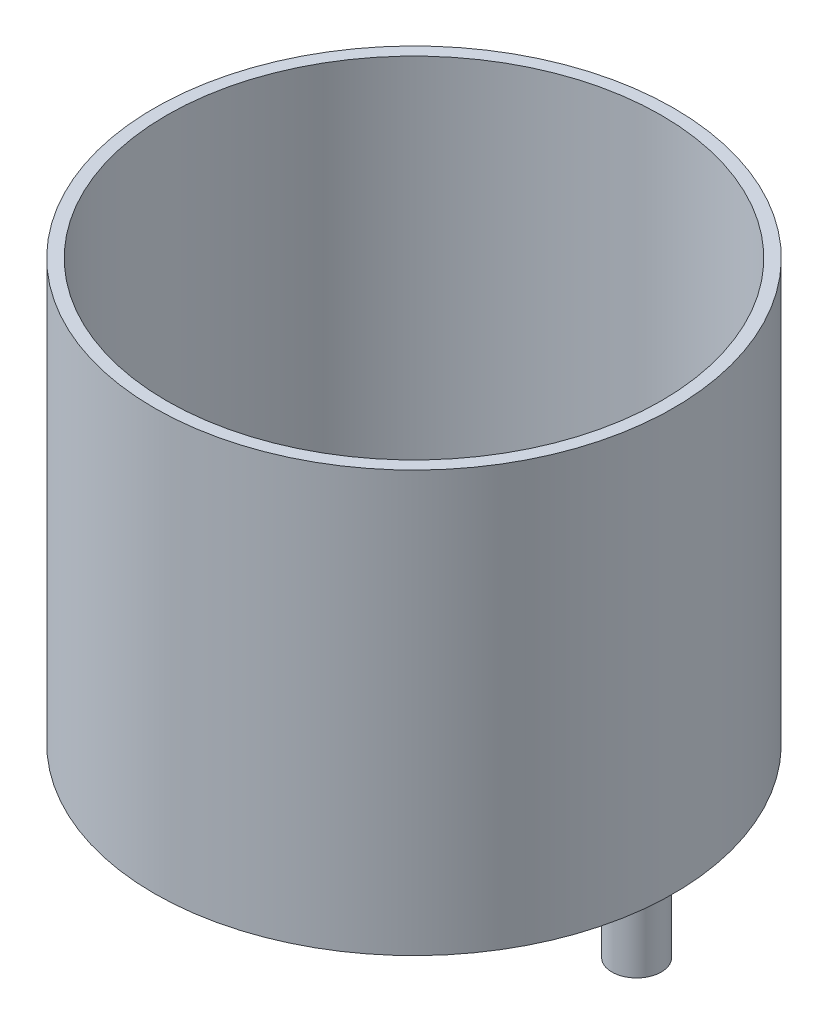
SolidWorks part; units mm, degrees
ref_plane "Front Plane" through (0, 0, 0) normal (0, 0, 1) x (1, 0, 0)
ref_plane "Top Plane" through (0, 0, 0) normal (0, 1, 0) x (1, 0, 0)
ref_plane "Right Plane" through (0, 0, 0) normal (1, 0, 0) x (0, 0, -1)
sketch "Compartment" plane through (0, 0, 0) normal (0, 0, 1) x (1, 0, 0)
  line L3 (105, -80) -> (0, -80)
  line L6 (100, 90) -> (105, 90)
  line L9 (100, 90) -> (100, -75)
  line L10 (100, -75) -> (0, -75)
  line L11 (0, -75) -> (0, -80)
  line L14 (105, 90) -> (105, -80)
  dimension "D1" = 165
  dimension "D2" = 5
  dimension "D5" = 100
  dimension "D6" = 5
  dimension "D9" = 80
ref_axis "Axis1" through (0, 0, 0) along (0, 1, 0)
revolve "Revolve1" add sketch "Compartment" angle 360 about axis through (0, 0, 0) along (0, 1, 0)
sketch "Motor Hole" plane through (0, -80, 0) normal (0, -1, 0) x (1, 0, 0)
  circle A0 centre (0, 0) radius 12.5
  dimension "D1" = 25
extrude "Cut-Extrude2" cut sketch "Motor Hole" against normal up to next
sketch "Stablizing poles" plane through (0, -80, 0) normal (0, -1, 0) x (1, 0, 0)
  circle A0 centre (-90, 0) radius 10
  circle A1 centre (90, 0) radius 10
  dimension "D1" = 20
  dimension "D2" = 90
  dimension "D3" = 90
extrude "Boss-Extrude1" add sketch "Stablizing poles" along normal blind 30
